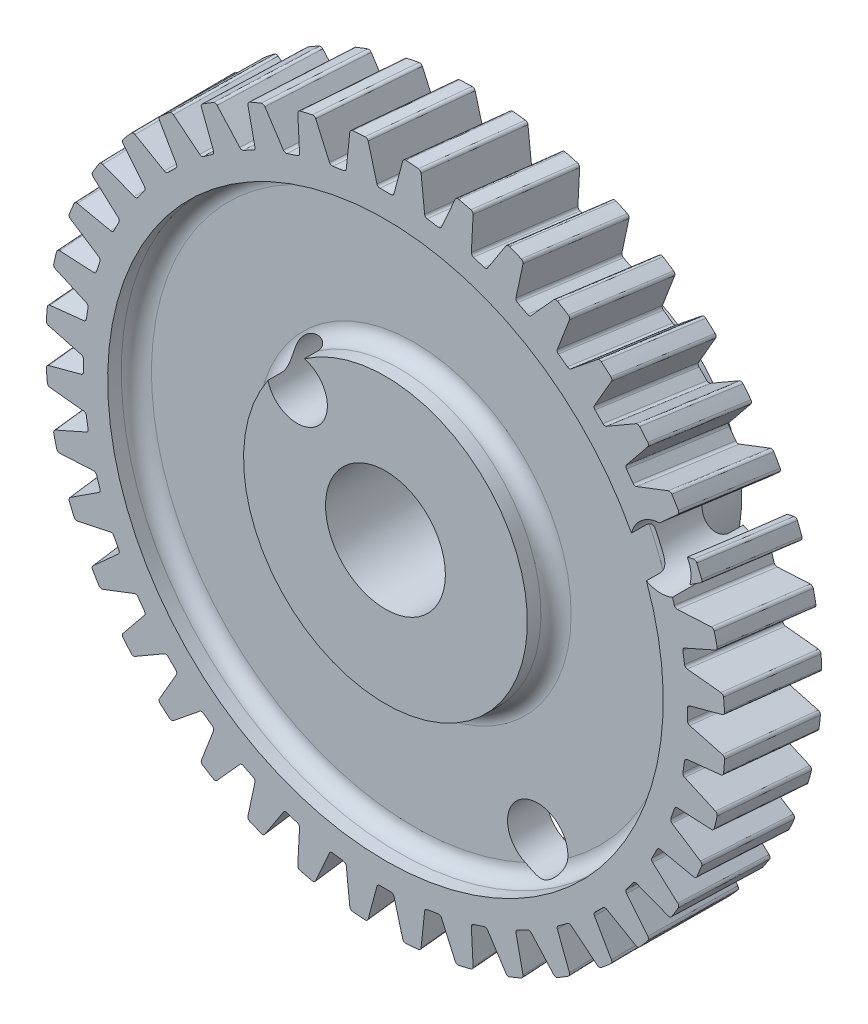
SolidWorks part; units mm, degrees
ref_plane "Front Plane" through (0, 0, 0) normal (0, 0, 1) x (1, 0, 0)
ref_plane "Top Plane" through (0, 0, 0) normal (0, 1, 0) x (1, 0, 0)
ref_plane "Right Plane" through (0, 0, 0) normal (1, 0, 0) x (0, 0, -1)
sketch "Sketch2" plane through (0, 0, 0) normal (1, 0, 0) x (0, 0, -1)
  line L0 (0, 0) -> (0, 22.5) construction
  line L1 (11, 3.9688) -> (-3.2, 3.9687)
  line L2 (-3.2, 3.9687) -> (-3.2, 9.4)
  line L3 (-3.2, 9.4) -> (-1.3, 9.4)
  line L4 (-1.3, 9.4) -> (-1.3, 18.4)
  line L5 (-1.3, 18.4) -> (-3.2, 18.4)
  line L6 (-3.2, 18.4) -> (-3.2, 22.5)
  line L7 (-3.2, 22.5) -> (3.2, 22.5)
  line L8 (3.2, 18.4) -> (3.2, 22.5)
  line L9 (1.3, 18.4) -> (3.2, 18.4)
  line L10 (1.3, 9.4) -> (1.3, 18.4)
  line L11 (3.2, 9.4) -> (1.3, 9.4)
  line L12 (3.2, 9.4) -> (11, 9.4)
  line L13 (11, 9.4) -> (11, 3.9688)
  line L14 (0, 0) -> (14.174, 0) construction
  dimension "D1" = 14.2
  dimension "D2" = 3.2
  dimension "D3" = 4.5
  dimension "D4" = 7.9375
  dimension "D5" = 9.4
  dimension "D6" = 9
  dimension "D7" = 22.5
  dimension "D8" = 6.4
revolve "Revolve1" add sketch "Sketch2" angle 360 about L14
fillet "Fillet1" radius 1 4 edges at (18.4, 0, 1.3) (9.4, 0, 1.3) (9.4, 0, -1.3) (18.4, 0, -1.3)
sketch "Sketch3" plane through (0, 0, 3.2) normal (0, 0, 1) x (1, 0, 0)
  line L0 (0, 22.6922) -> (0, 20) construction
  line L1 (-0.525, 20) -> (0.525, 20)
  line L2 (0.525, 20) -> (1.2464, 22.6922)
  line L3 (1.2464, 22.6922) -> (-1.2464, 22.6922)
  line L4 (-0.525, 20) -> (-1.2464, 22.6922)
  dimension "D1" = 20
  dimension "D2" = 1.05
  dimension "D3" = 15
sketch "Sketch4" plane through (0, 0, 0) normal (0, 1, 0) x (1, 0, 0)
  line L0 (0, -3.2) -> (0.691, 3.2)
  line L1 (1.2464, -3.2) -> (-1.2464, -3.2) construction
  line L2 (22.5, 3.2) -> (-22.5, 3.2) construction
sweep "Cut-Sweep1" cut profiles "Sketch3" path "Sketch4"
pattern_circular "CirPattern1" count 40 over 360 about axis through (0, 0, 3.2) along (0, 0, 1) of "Cut-Sweep1"
fillet "Fillet2" radius 0.2 160 edges at (1.526, 22.4482, 0.0047) (0.8705, 20, 0) (-0.8445, 22.4841, -0.0056) (-2.0045, 22.4105, 0.0047) (-2.2689, 19.8899, 0) (-3.306, 19.7257, 0) (-4.3514, 22.0752, -0.0056) (-5.4856, 21.8211, 0.0047) (-5.3525, 19.2901, 0) (-6.3511, 18.9657, 0) (-7.7512, 21.1227, -0.0056) (-8.8316, 20.6943, 0.0047) (-8.3042, 18.2153, 0) (-9.2398, 17.7386, 0) (-10.9601, 19.6501, -0.0056) (-11.9602, 19.0579, 0.0047) (-11.0515, 16.692, 0) (-11.9009, 16.0748, 0) (-13.8991, 17.6936, -0.0056) (-14.7943, 16.9523, 0.0047) (-13.5266, 14.7577, 0) (-14.2691, 14.0152, 0) (-16.4959, 15.3015, -0.0056) (-17.264, 14.4292, 0.0047) (-15.6687, 12.4599, 0) (-16.2859, 11.6105, 0) (-18.6865, 12.5326, -0.0056) (-19.3087, 11.5509, 0.0047) (-17.4249, 9.8554, 0) (-17.9016, 8.9199, 0) (-20.4169, 9.4551, -0.0056) (-20.878, 8.3882, 0.0047) (-18.7521, 7.0082, 0) (-19.0766, 6.0096, 0) (-21.6447, 6.1448, -0.0056) (-21.9331, 5.0188, 0.0047) (-19.6176, 3.9885, 0) (-19.7818, 2.9514, 0) (-22.3394, 2.6832, -0.0056) (-22.4482, 1.526, 0.0047) (-20, 0.8705, 0) (-20, -0.1795, 0) (-22.4841, -0.8445, -0.0056) (-22.4105, -2.0045, 0.0047) (-19.8899, -2.2689, 0) (-19.7257, -3.306, 0) (-22.0752, -4.3514, -0.0056) (-21.8211, -5.4856, 0.0047) (-19.2901, -5.3525, 0) (-18.9657, -6.3511, 0) (-21.1227, -7.7512, -0.0056) (-20.6943, -8.8316, 0.0047) (-18.2153, -8.3042, 0) (-17.7386, -9.2398, 0) (-19.6501, -10.9601, -0.0056) (-19.0579, -11.9602, 0.0047) (-16.692, -11.0515, 0) (-16.0748, -11.9009, 0) (-17.6936, -13.8991, -0.0056) (-16.9523, -14.7943, 0.0047) (-14.7577, -13.5266, 0) (-14.0152, -14.2691, 0) (-15.3015, -16.4959, -0.0056) (-14.4292, -17.264, 0.0047) (-12.4599, -15.6687, 0) (-11.6105, -16.2859, 0) (-12.5326, -18.6865, -0.0056) (-11.5509, -19.3087, 0.0047) (-9.8554, -17.4249, 0) (-8.9199, -17.9016, 0) (-9.4551, -20.4169, -0.0056) (-8.3882, -20.878, 0.0047) (-7.0082, -18.7521, 0) (-6.0096, -19.0766, 0) (-6.1448, -21.6447, -0.0056) (-5.0188, -21.9331, 0.0047) (-3.9885, -19.6176, 0) (-2.9514, -19.7818, 0) (-2.6832, -22.3394, -0.0056) (-1.526, -22.4482, 0.0047) (-0.8705, -20, 0) (0.1795, -20, 0) (0.8445, -22.4841, -0.0056) (2.0045, -22.4105, 0.0047) (2.2689, -19.8899, 0) (3.306, -19.7257, 0) (4.3514, -22.0752, -0.0056) (5.4856, -21.8211, 0.0047) (5.3525, -19.2901, 0) (6.3511, -18.9657, 0) (7.7512, -21.1227, -0.0056) (8.8316, -20.6943, 0.0047) (8.3042, -18.2153, 0) (9.2398, -17.7386, 0) (10.9601, -19.6501, -0.0056) (11.9602, -19.0579, 0.0047) (11.0515, -16.692, 0) (11.9009, -16.0748, 0) (13.8991, -17.6936, -0.0056) (14.7943, -16.9523, 0.0047) (13.5266, -14.7577, 0) (14.2691, -14.0152, 0) (16.4959, -15.3015, -0.0056) (17.264, -14.4292, 0.0047) (15.6687, -12.4599, 0) (16.2859, -11.6105, 0) (18.6865, -12.5326, -0.0056) (19.3087, -11.5509, 0.0047) (17.4249, -9.8554, 0) (17.9016, -8.9199, 0) (20.4169, -9.4551, -0.0056) (20.878, -8.3882, 0.0047) (18.7521, -7.0082, 0) (19.0766, -6.0096, 0) (21.6447, -6.1448, -0.0056) (21.9331, -5.0188, 0.0047) (19.6176, -3.9885, 0) (19.7818, -2.9514, 0) (22.3394, -2.6832, -0.0056) (22.4482, -1.526, 0.0047) (20, -0.8705, 0) (20, 0.1795, 0) (22.4841, 0.8445, -0.0056) (22.4105, 2.0045, 0.0047) (19.8899, 2.2689, 0) (19.7257, 3.306, 0) (22.0752, 4.3514, -0.0056) (21.8211, 5.4856, 0.0047) (19.2901, 5.3525, 0) (18.9657, 6.3511, 0) (21.1227, 7.7512, -0.0056) (20.6943, 8.8316, 0.0047) (18.2153, 8.3042, 0) (17.7386, 9.2398, 0) (19.6501, 10.9601, -0.0056) (19.0579, 11.9602, 0.0047) (16.692, 11.0515, 0) (16.0748, 11.9009, 0) (17.6936, 13.8991, -0.0056) (16.9523, 14.7943, 0.0047) (14.7577, 13.5266, 0) (14.0152, 14.2691, 0) (15.3015, 16.4959, -0.0056) (14.4292, 17.264, 0.0047) (12.4599, 15.6687, 0) (11.6105, 16.2859, 0) (12.5326, 18.6865, -0.0056) (11.5509, 19.3087, 0.0047) (9.8554, 17.4249, 0) (8.9199, 17.9016, 0) (9.4551, 20.4169, -0.0056) (8.3882, 20.878, 0.0047) (7.0082, 18.7521, 0) (6.0096, 19.0766, 0) (6.1448, 21.6447, -0.0056) (5.0188, 21.9331, 0.0047) (3.9885, 19.6176, 0) (2.9514, 19.7818, 0) (2.6832, 22.3394, -0.0056) (-0.1795, 20, 0)
ref_axis "gear axis" through (0, 0, -11) along (0, 0, 1)
hole_wizard "Ø4.0 (4) Diameter Hole1" positions "Sketch5" profile "Sketch6" hole size "Ø4.0" standard "ISO" end condition through all
sketch "Sketch5" plane through (66.6178, -178.24, 3.9366) normal (0, 0, 1) x (1, -0.0054, 0)
  circle A5 centre (-60.718, 177.8786) radius 13.9687
  point P0 (-73.4549, 183.6142)
  point P2 (-49.3823, 186.0412)
  point P4 (-59.3167, 163.9803)
sketch "Sketch6" plane through (-5.8471, 5.7672, 3.9366) normal (1, 0, 0) x (0, -1, 0)
  line L0 (0, 0) -> (0, 14.9366)
  line L1 (0, 14.9366) -> (2, 14.9366)
  line L2 (2, 14.9366) -> (2, 0)
  line L3 (2, 0) -> (0, 0)
  line L4 (0, -6.35) -> (0, 107.95) construction
  dimension "Thru Hole Dia." = 4
  dimension "Thru Hole Depth" = 14.9366
